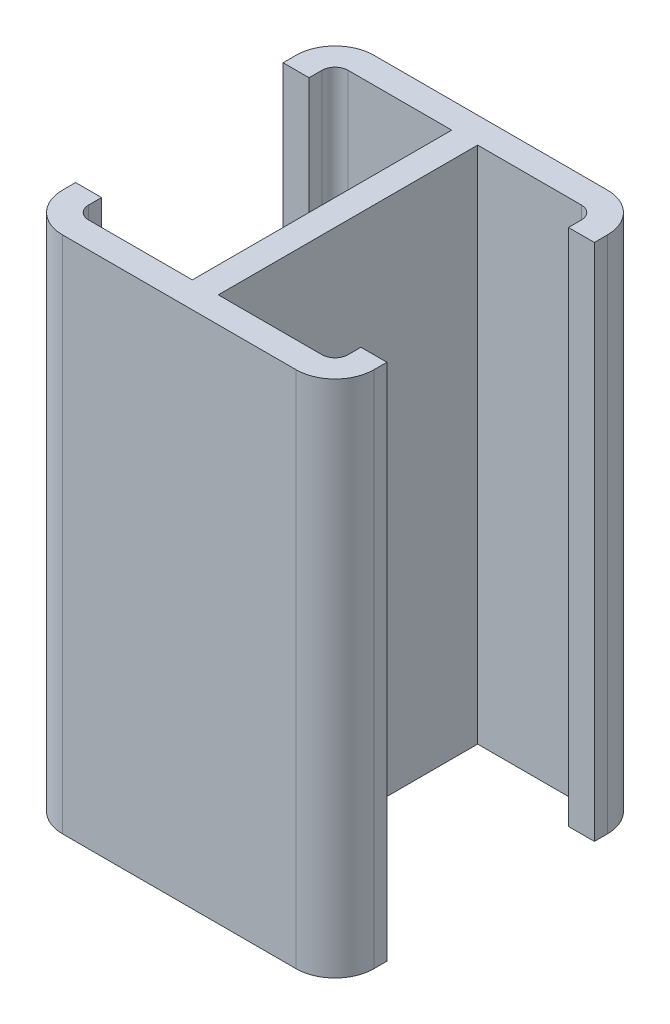
SolidWorks part; units mm, degrees
ref_plane "正面" through (0, 0, 0) normal (0, 0, 1) x (1, 0, 0)
ref_plane "平面" through (0, 0, 0) normal (0, 1, 0) x (1, 0, 0)
ref_plane "右側面" through (0, 0, 0) normal (1, 0, 0) x (0, 0, -1)
sketch "ｽｹｯﾁ1" plane through (0, 0, 0) normal (0, 1, 0) x (1, 0, 0)
  line L0 (0, 0) -> (0, -60)
  line L1 (0, -60) -> (45, -60)
  line L2 (60, -45) -> (60, -40)
  line L3 (60, -40) -> (50, -40)
  line L4 (50, -40) -> (50, -45)
  line L5 (45, -50) -> (5, -50)
  line L6 (5, -50) -> (5, 0)
  line L7 (5, 0) -> (0, 0)
  arc A0 (60, -45) -> (45, -60) centre (45, -45) cw
  arc A1 (50, -45) -> (45, -50) centre (45, -45) cw
  point P11 (60, -60)
  point P14 (50, -50)
  dimension "D7" = 15
  dimension "D8" = 5
  dimension "D1" = 60
  dimension "D2" = 60
  dimension "D3" = 20
  dimension "D4" = 10
  dimension "D5" = 10
  dimension "D6" = 5
extrude "ﾎﾞｽ - 押し出し1" add sketch "ｽｹｯﾁ1" along normal blind 200
mirror "ﾐﾗｰ1" about plane through (0, 200, 0) normal (1, 0, 0) of bodies 101
mirror "ﾐﾗｰ2" about plane through (5, 200, 0) normal (0, 0, 1) of bodies 104
equation "\"C\"= 20"
equation "\"D3@ｽｹｯﾁ1\"=\"C\""
equation "\"B\"= 10"
equation "\"D4@ｽｹｯﾁ1\"=\"B\""
equation "\"D5@ｽｹｯﾁ1\"=\"B\""
equation "\"A\"= 10"
equation "\"D6@ｽｹｯﾁ1\"=\"A\"/2"
equation "\"D8@ｽｹｯﾁ1\"= \"B\"/2"
equation "\"D7@ｽｹｯﾁ1\"= \"B\"/2*3"
